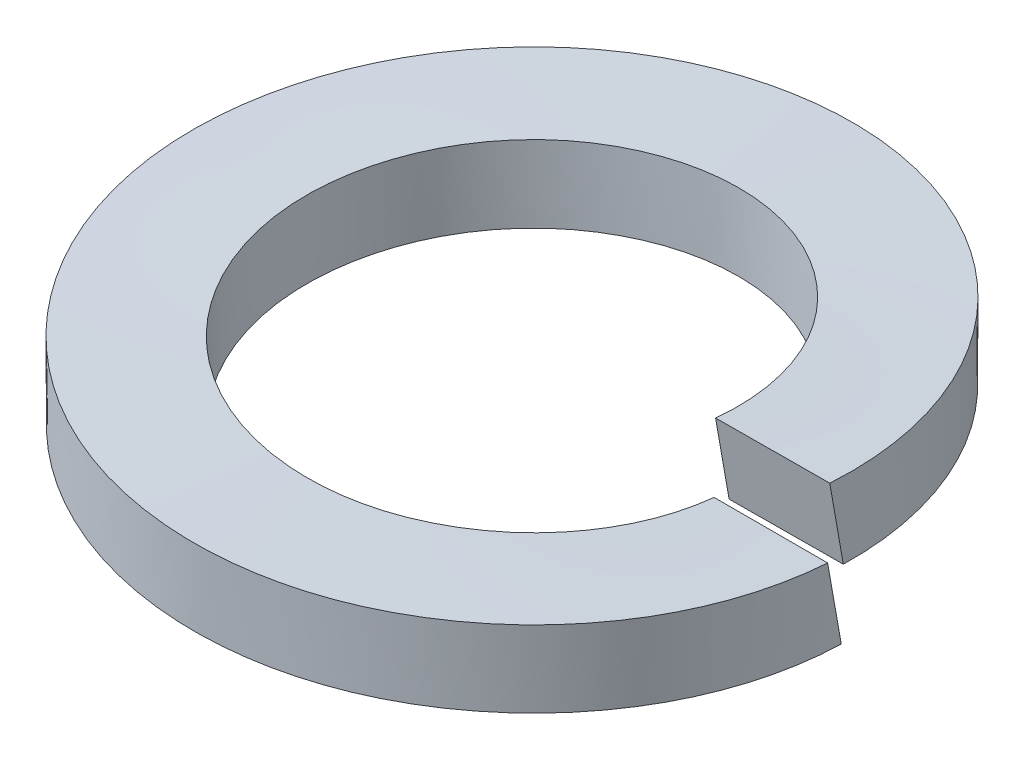
SolidWorks part; units mm, degrees
material "AISI 304"
ref_plane "Front Plane" through (0, 0, 0) normal (0, 0, 1) x (1, 0, 0)
ref_plane "Top Plane" through (0, 0, 0) normal (0, 1, 0) x (1, 0, 0)
ref_plane "Right Plane" through (0, 0, 0) normal (1, 0, 0) x (0, 0, -1)
sketch "Washer ID" plane through (0, 0, 0) normal (0, 1, 0) x (1, 0, 0)
  line L0 (0, 0) -> (9.5, 0) construction
  circle A0 centre (0, 0) radius 9.5
  dimension "Washer ID" = 19
ref_plane "Plane" through (0, 0, 0) normal (0, -0.1736, 0.9848) x (1, 0, 0)
sketch "Profile Height" plane through (0, 0, 0) normal (0, 0, 1) x (1, 0, 0)
  line L0 (0, 0) -> (0, 3.5) construction
  dimension "T" = 3.5
sketch "Sweep Profile" plane through (0, 0, 0) normal (0, -0.1736, 0.9848) x (1, 0, 0)
  line L1 (9.5, 3.4468) -> (14.5, 3.4468)
  line L2 (9.5, 3.4468) -> (9.5, 0)
  line L3 (9.5, 0) -> (14.5, 0)
  line L4 (14.5, 3.4468) -> (14.5, 0)
  dimension "B" = 5
  dimension "D2" = 3.4468
curve "Helix/Spiral1" pitch 3.003 height 3 radius 9.5 left hand yes centre (0, 0, 0) axis (0, 1, 0) start towards (1, 0, 0)
sweep "Sweep" add profiles "Sweep Profile" path "Helix/Spiral1"
